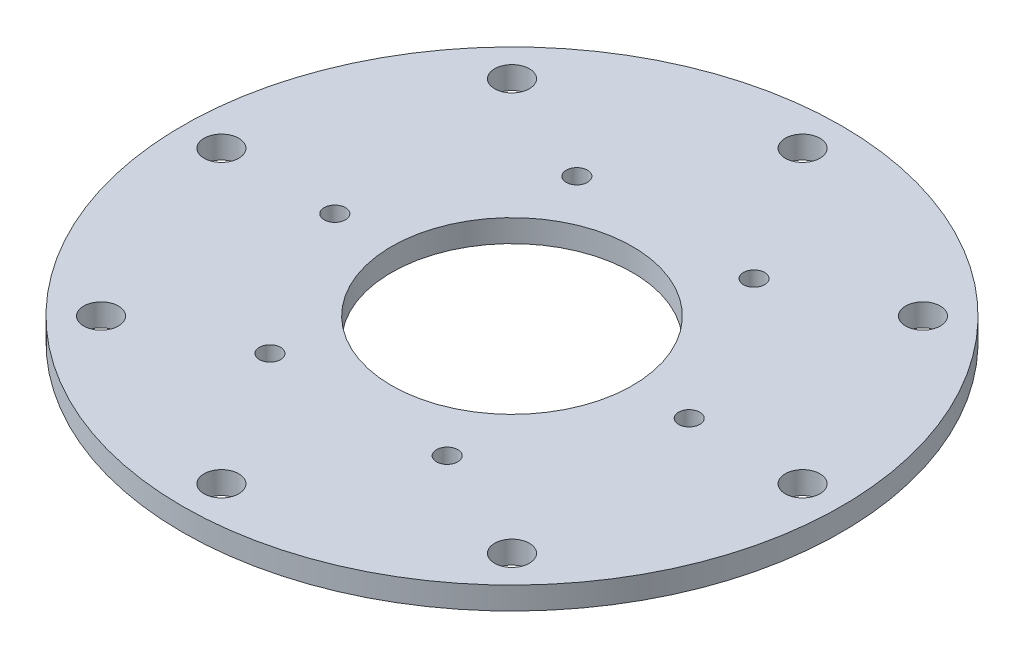
SolidWorks part; units mm, degrees
material "1060 Alloy"
ref_plane "Front Plane" through (0, 0, 0) normal (0, 0, 1) x (1, 0, 0)
ref_plane "Top Plane" through (0, 0, 0) normal (0, 1, 0) x (1, 0, 0)
ref_plane "Right Plane" through (0, 0, 0) normal (1, 0, 0) x (0, 0, -1)
sketch "Sketch2" plane through (0, 0, 0) normal (0, 1, 0) x (1, 0, 0)
  circle A0 centre (0, 0) radius 17
  circle A1 centre (0, 0) radius 46.5
  circle A2 centre (0, 0) radius 41 construction
  circle A3 centre (-41, 0) radius 2.45
  circle A4 centre (0, 0) radius 25 construction
  circle A5 centre (-25, 0) radius 1.5
  circle A6 centre (-12.5, 21.6506) radius 1.5
  circle A7 centre (12.5, 21.6506) radius 1.5
  circle A8 centre (25, 0) radius 1.5
  circle A9 centre (12.5, -21.6506) radius 1.5
  circle A10 centre (-12.5, -21.6506) radius 1.5
  circle A11 centre (-28.9914, 28.9914) radius 2.45
  circle A12 centre (0, 41) radius 2.45
  circle A13 centre (28.9914, 28.9914) radius 2.45
  circle A14 centre (41, 0) radius 2.45
  circle A15 centre (28.9914, -28.9914) radius 2.45
  circle A16 centre (0, -41) radius 2.45
  circle A17 centre (-28.9914, -28.9914) radius 2.45
  point P22 (0, 0)
  point P23 (0, 0)
  point P24 (0, 0)
  point P33 (0, 0)
  point P34 (0, 0)
  dimension "D1" = 3
  dimension "D2" = 50
  dimension "D4" = 34
  dimension "D5" = 93
  dimension "D6" = 82
  dimension "D7" = 4.9
  dimension "D3" = 6
  dimension "D8" = 8
extrude "Boss-Extrude1" add sketch "Sketch2" along normal blind 3.175
equation "\"Stator_OD\"= 60'No Tolerance given"
equation "\"A\"=35.81 'taken off spec sheet for 06808 (A)"
equation "\"Rotor_ID\"= 30'No Tolerance Given"
equation "\"back_bearing_Thickness\"= 5'-0.12"
equation "\"back_bearing_OD\"= 24'-0.009 https://www.mcmaster.com/5972K155/"
equation "\"Stator_Gap\"= 0.0375'+- 0.0125 (From 1.3.3.1 Kollmorgen manual)"
equation "\"Back_mount_hole\"= 1.75'To be tapped to M2 (USE LOCKTITE)"
equation "\"facePlate_Mount_Hole\"= 2.75'To be tapped to M3"
equation "\"final_shaftD\"= 12'To fit in harmonic"
equation "\"final_shaftL\"= 5.25+3+\"sheet_thick\"+\"connector_thick\"-3+\"harmon_coupleL\"+0.5-\"shaft_Ladjust\"'length to make everything nice and aligned"
equation "\"back_bearing_ID\"= 15'"
equation "\"back_bearing_IDOD\"= 16.5'measured off CAD, actually 16.75, but rounded down to nicer number"
equation "\"rotor_shaftD\"= \"Rotor_ID\" - (\"rotor-shaft_gap\")*2'"
equation "\"front_bearing_ID\"= 12'https://www.mcmaster.com/5972K154/"
equation "\"front_bearing_OD\"= 21'-0.009"
equation "\"front_bearing_IDOD\"= 13.5'Measured off CAD. Actually 13.75, but rounded down"
equation "\"rotor-shaft_gap\" = 0.0185 '+-0.0065 (from manual)"
equation "\"front_bearing_Thickness\"= 5'-0.12"
equation "\"rotor_thickness\"= 2.4'measured off CAD"
equation "\"rotor_height\"= 32.86'+-0.075 taken off spec sheet for 06826 (C)"
equation "\"B\"= 26.3'+-0.35 taken off spec sheet for 06826"
equation "\"key_L\"= 20'-0.2 https://www.mcmaster.com/2977N19/"
equation "\"key_H\"= 4'-0.03"
equation "\"key_W\"= 4'-0.03"
equation "\"harmon_keyH\"= 13.8'+0.1 from drawing"
equation "\"harmon_coupleL\"= 21.5' taken from drawing https://www.harmonicdrive.net/_hd/content/caddownloads/dxf/csg-2uh-lw_gearheads/csg-20-100-2uh-lw.pdf"
equation "\"harmon_diam\"= 93' from drawing"
equation "\"harmon_BCD\"= 82' from drawing"
equation "\"harmon_holeD1\"= 5.5' from drawing"
equation "\"harmon_holeD2\"= 5' from drawing"
equation "\"harmon_holeAng\"= 22.5' from drawing"
equation "\"sheet_thick\"= 1/8*25.4 'random, replace w actual sheet thickness when u feel like :)"
equation "\"D1@Sketch2\"=\"facePlate_Mount_Hole\"+0.25"
equation "\"D4@Sketch2\"=\"back_bearing_OD\"+10"
equation "\"D5@Sketch2\"=\"harmon_diam\""
equation "\"D6@Sketch2\"=\"harmon_BCD\""
equation "\"D7@Sketch2\"=\"harmon_holeD2\"-0.1"
equation "\"D1@Boss-Extrude1\"=\"sheet_thick\""
equation "\"nut-thickness\"= 5 'idk measure the ones in the shop and adjust"
equation "\"connector_thick\"= 10' random for now"
equation "\"shaft_Ladjust\"= 6.5' sorry. It's silly, but it works."
